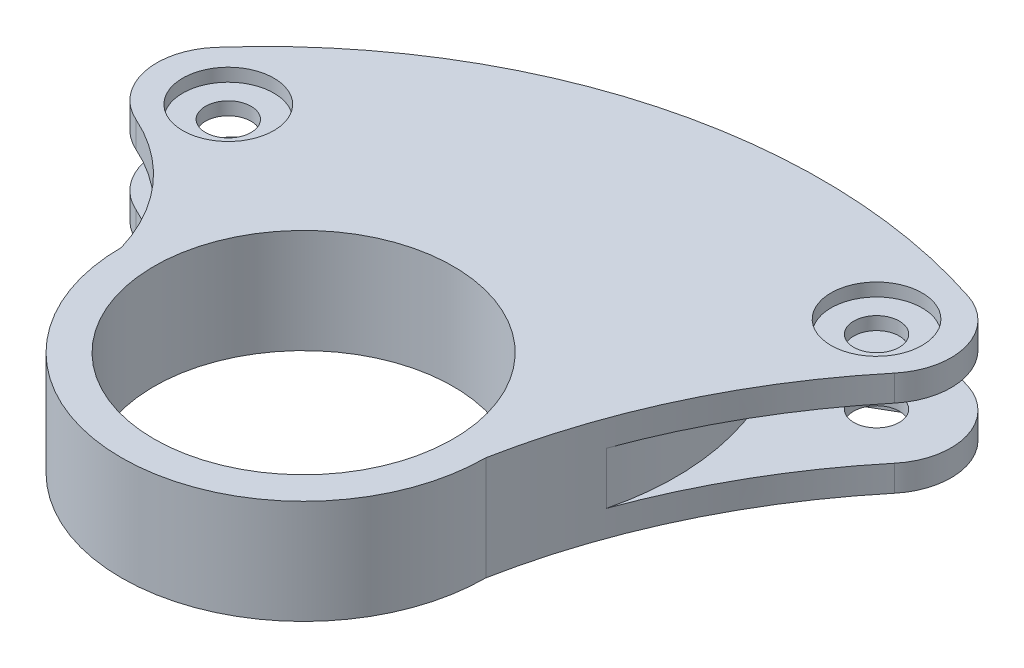
SolidWorks part; units mm, degrees
material "ABS"
ref_plane "Front Plane" through (0, 0, 0) normal (0, 0, 1) x (1, 0, 0)
ref_plane "Top Plane" through (0, 0, 0) normal (0, 1, 0) x (1, 0, 0)
ref_plane "Right Plane" through (0, 0, 0) normal (1, 0, 0) x (0, 0, -1)
sketch "Sketch1" plane through (0, 0, 0) normal (0, 1, 0) x (1, 0, 0)
  line L0 (14, 0) -> (28.7924, 26.2713) construction
  line L3 (-28.4978, 10.3171) -> (-14, 0) construction
  line L4 (-14, 0) -> (-14, -14.226) construction
  line L5 (14, 0) -> (14, -13.6969) construction
  circle A0 centre (0, 0) radius 11.5
  circle A1 centre (0, 0) radius 14 construction
  arc A2 (-14, 0) -> (-28.4978, 10.3171) centre (-27.8477, -4.1142) ccw
  arc A3 (14, 0) -> (28.7924, 26.2713) centre (60.6131, -8.9459) cw
  arc A4 (-28.4978, 10.3171) -> (28.7924, 26.2713) centre (8.4154, -11.3957) cw
  arc A5 (-14, 0) -> (14, 0) centre (0, 0) ccw
  dimension "D1" = 23
  dimension "D3" = 30.1496
  dimension "D4" = 17.7941
  dimension "D5" = 125.437
  dimension "D6" = 150.618
  dimension "D2" = 2.5
extrude "Boss-Extrude1" add sketch "Sketch1" along normal blind 8
fillet "Fillet1" radius 5 2 edges at (-28.4978, 4, -10.3171) (28.7924, 4, -26.2713)
sketch "Sketch2" plane through (0, 8, 0) normal (0, 1, 0) x (1, 0, 0)
  line L0 (0, 0) -> (-19.4182, 13.6298) construction
  line L2 (19.7922, 24.244) -> (0, 0) construction
  line L3 (-24.8183, 12.5861) -> (-19.4182, 13.6298) construction
  line L4 (25.0295, 25.9234) -> (19.7922, 24.244) construction
  circle A0 centre (19.7922, 24.244) radius 1.75
  circle A1 centre (-19.4182, 13.6298) radius 1.75
  circle A2 centre (-19.4182, 13.6298) radius 3.5 construction
  circle A3 centre (19.7922, 24.244) radius 3.5 construction
  arc A4 (-23.6795, 16.9583) -> (-21.9676, 9.0808) centre (-19.9323, 13.6479) ccw construction
  arc A5 (24.0741, 21.3478) -> (21.786, 29.2891) centre (20.2249, 24.5391) ccw construction
  dimension "D1" = 3.5
  dimension "D2" = 3.5
  dimension "D3" = 7
  dimension "D4" = 7
  dimension "D5" = 5.5
  dimension "D6" = 5.5
  dimension "D7" = 31.297
  dimension "D8" = 23.7242
extrude "Cut-Extrude1" cut sketch "Sketch2" against normal through all
ref_plane "Plane1" through (0, 4, 0) normal (0, 1, 0) x (1, 0, 0)
sketch "Sketch4" plane through (0, 4, 0) normal (0, 1, 0) x (1, 0, 0)
  line L0 (1.8351, 30.9213) -> (2.851, 31.9372)
  line L1 (2.851, 31.9372) -> (26.3152, 31.9372)
  line L2 (26.3152, 31.9372) -> (26.3152, 18.8713)
  line L3 (26.3152, 18.8713) -> (16.0052, 7.2697)
  line L4 (-7.3932, 28.4053) -> (-8.9693, 29.2135)
  line L5 (-8.9693, 29.2135) -> (-26.2189, 19.3499)
  line L6 (-26.2189, 19.3499) -> (-26.2189, 10.3745)
  line L7 (-26.2189, 10.3745) -> (-15.1004, 2.6823)
  arc A0 (1.8351, 30.9213) -> (16.0052, 7.2697) centre (-2.9056, 12.0105) cw
  arc A1 (21.786, 29.2891) -> (-23.6795, 16.9583) centre (8.4154, -11.3957) ccw construction
  arc A2 (24.0741, 21.3478) -> (14, 0) centre (60.6131, -8.9459) ccw construction
  arc A3 (-15.1004, 2.6823) -> (-7.3932, 28.4053) centre (8.4731, 9.6352) cw
  arc A4 (-14, 0) -> (-21.9676, 9.0808) centre (-27.8477, -4.1142) ccw construction
extrude "Cut-Extrude2" cut sketch "Sketch4" against normal blind 2 and the other way blind 2
sketch "Sketch5" plane through (0, 0, 0) normal (0, -1, 0) x (1, 0, 0)
  line L1 (-16.4061, -14.8046) -> (-16.8947, -11.6086)
  line L2 (-16.8947, -11.6086) -> (-19.9069, -10.4338)
  line L3 (-19.9069, -10.4338) -> (-22.4304, -12.455)
  line L4 (-22.4304, -12.455) -> (-21.9417, -15.651)
  line L5 (-21.9417, -15.651) -> (-18.9296, -16.8258)
  line L6 (-18.9296, -16.8258) -> (-16.4061, -14.8046)
  line L7 (19.7922, -21.0109) -> (16.9922, -22.6274)
  line L8 (16.9922, -22.6274) -> (16.9922, -25.8606)
  line L9 (16.9922, -25.8606) -> (19.7922, -27.4772)
  line L10 (19.7922, -27.4772) -> (22.5922, -25.8606)
  line L11 (22.5922, -25.8606) -> (22.5922, -22.6274)
  line L12 (22.5922, -22.6274) -> (19.7922, -21.0109)
  circle A0 centre (-19.4182, -13.6298) radius 2.8 construction
  circle A1 centre (19.7922, -24.244) radius 2.8 construction
  dimension "D1" = 5.6
  dimension "D2" = 5.6
extrude "Cut-Extrude3" cut sketch "Sketch5" against normal blind 1
sketch "Sketch6" plane through (0, 8, 0) normal (0, 1, 0) x (1, 0, 0)
  circle A0 centre (-19.4182, 13.6298) radius 3.5
  circle A1 centre (19.7922, 24.244) radius 3.5
  dimension "D1" = 7
  dimension "D2" = 7
extrude "Cut-Extrude4" cut sketch "Sketch6" against normal blind 1
